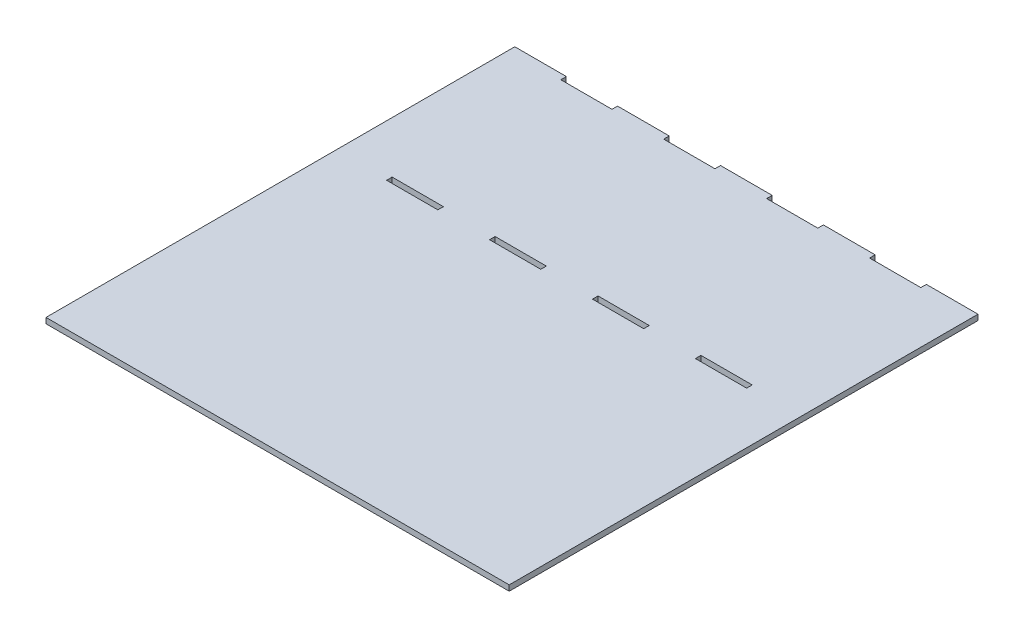
SolidWorks part; units mm, degrees
material "Pine"
ref_plane "Front Plane" through (0, 0, 0) normal (0, 0, 1) x (1, 0, 0)
ref_plane "Top Plane" through (0, 0, 0) normal (0, 1, 0) x (1, 0, 0)
ref_plane "Right Plane" through (0, 0, 0) normal (1, 0, 0) x (0, 0, -1)
sketch "Sketch2" plane through (0, 0, 0) normal (0, 1, 0) x (1, 0, 0)
  line L1 (-250, -253) -> (250, -253)
  line L2 (-250, -253) -> (-250, 253)
  line L3 (-250, 253) -> (250, 253)
  line L4 (250, -253) -> (250, 253)
  line L5 (-250, -253) -> (250, 253) construction
  line L6 (-250, 253) -> (250, -253) construction
  point P0 (0, 0)
  dimension "D1" = 500
  dimension "D2" = 506
extrude "Boss-Extrude1" add sketch "Sketch2" along normal blind 6
sketch "Sketch3" plane through (0, 6, 0) normal (0, 1, 0) x (1, 0, 0)
  line L0 (250, 253) -> (-250, 253) construction
  line L1 (194.4, 253) -> (138.8, 253)
  line L2 (194.4, 253) -> (194.4, 247)
  line L3 (194.4, 247) -> (138.8, 247)
  line L4 (138.8, 253) -> (138.8, 247)
  line L5 (250, -253) -> (250, 253) construction
  ellipse E0 centre (194.4, 250) end of major axis (194.4, 247) minor radius 0.2
  ellipse E1 centre (138.8, 250) end of major axis (138.8, 247) minor radius 0.2
  line M6 (250, 253) -> (-250, 253)
  dimension "D1" = 6
  dimension "D2" = 55.6
  dimension "D3" = 55.6
  dimension "D4" = 0.2
  dimension "D5" = 0.2
extrude "Cut-Extrude1" cut sketch "Sketch3" against normal blind 6 contours E1 L3 E0 M6 region at (166.6, 6, -250)
pattern_linear "LPattern1" count 4 spacing 111.1 along (-1, 0, 0) of "Cut-Extrude1"
pattern_linear "LPattern2" count 2 spacing 188 along (0, 0, 1) of "Cut-Extrude1"
pattern_linear "LPattern3" count 4 spacing 111.1 along (-1, 0, 0) of "LPattern2"
